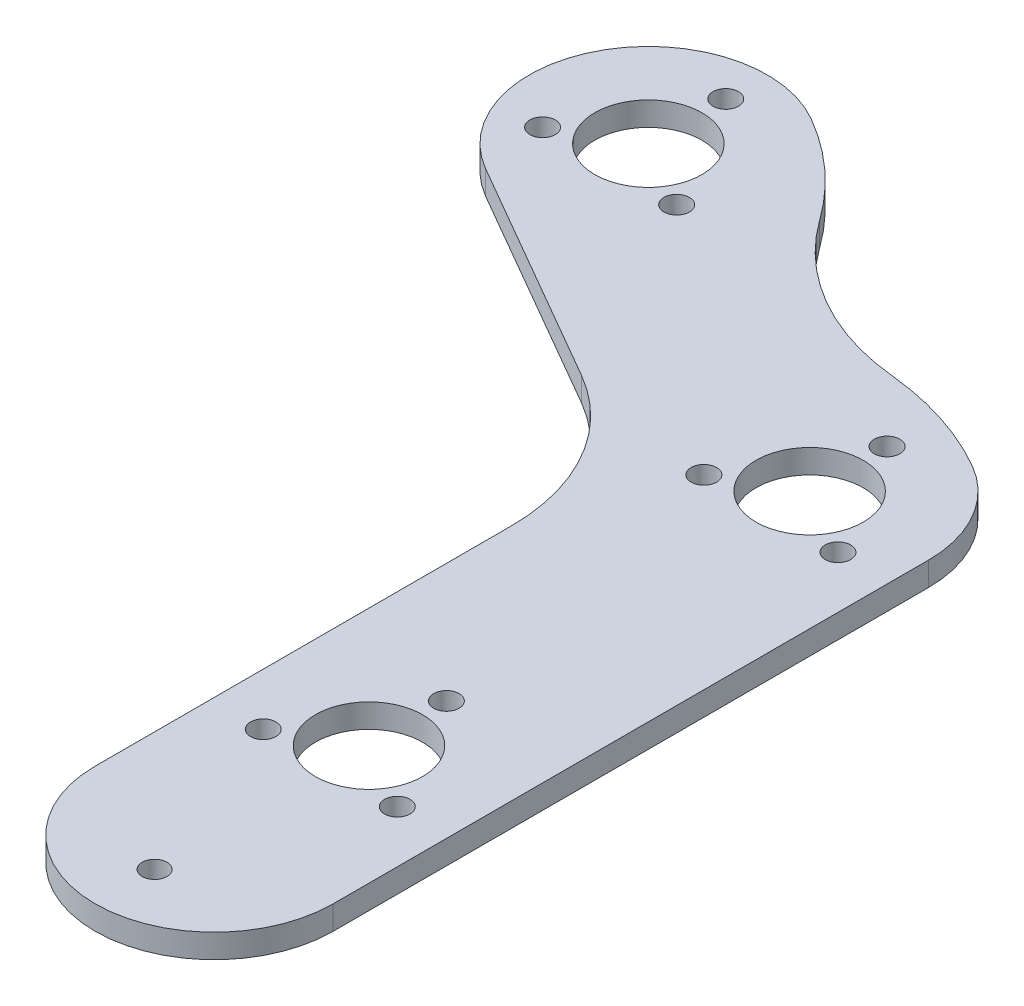
SolidWorks part; units mm, degrees
material "PC High Viscosity"
ref_plane "Front Plane" through (0, 0, 0) normal (0, 0, 1) x (1, 0, 0)
ref_plane "Top Plane" through (0, 0, 0) normal (0, 1, 0) x (1, 0, 0)
ref_plane "Right Plane" through (0, 0, 0) normal (1, 0, 0) x (0, 0, -1)
sketch "Sketch2" plane through (0, 0, 0) normal (0, 1, 0) x (1, 0, 0)
  line L0 (0, 117.475) -> (0, 0) construction
  line L1 (0, 117.475) -> (-101.7363, 176.2125) construction
  line L2 (31.75, 20.032) -> (31.75, 117.475)
  line L4 (-57.15, 113.8088) -> (-117.6113, 148.7162)
  line L5 (-59.8623, 248.7404) -> (-151.9577, 89.2265) construction
  line L6 (-85.8613, 203.7088) -> (15.875, 144.9713) construction
  line L7 (59.941, 221.2959) -> (-45.6102, 38.4758) construction
  line L8 (-50.8682, 146.8437) -> (-34.9932, 174.3401) construction
  line L9 (-34.9932, 174.3401) -> (22.5602, 274.0254) construction
  line L10 (-31.75, -41.275) -> (-31.75, 69.8147)
  line L11 (31.75, 20.032) -> (31.75, -41.275)
  circle A1 centre (0, 0) radius 14.2875
  circle A2 centre (0, 117.475) radius 14.2875
  circle A3 centre (-101.7363, 176.2125) radius 14.2875
  arc A5 (-117.6113, 148.7162) -> (-85.8613, 203.7088) centre (-101.7363, 176.2125) cw
  arc A6 (31.75, 117.475) -> (15.875, 144.9713) centre (0, 117.475) ccw
  arc A7 (-31.75, 69.8147) -> (-57.15, 113.8088) centre (-82.55, 69.8147) ccw
  circle A8 centre (-101.7363, 176.2125) radius 50.8 construction
  circle A9 centre (0, 117.475) radius 50.8 construction
  arc A12 (31.75, -41.275) -> (-31.75, -41.275) centre (0, -41.275) cw
  circle A16 centre (0, -57.15) radius 3.302
  arc A18 (15.875, 144.9713) -> (-15.7886, 155.1371) centre (-23.4652, 76.832) ccw
  arc A19 (-15.7886, 155.1371) -> (-61.2257, 181.3702) centre (-9.5932, 218.3341) cw
  arc A20 (-61.2257, 181.3702) -> (-85.8613, 203.7088) centre (-125.2016, 135.5695) ccw
  circle A21 centre (-17.8726, -10.3187) radius 3.3909
  circle A22 centre (0, 20.6375) radius 3.3909
  circle A23 centre (17.8726, -10.3187) radius 3.3909
  circle A24 centre (-17.8726, 107.1563) radius 3.3909
  circle A25 centre (-119.6089, 165.8938) radius 3.3909
  circle A26 centre (0, 138.1125) radius 3.3909
  circle A27 centre (17.8726, 107.1563) radius 3.3909
  circle A28 centre (-101.7363, 196.85) radius 3.3909
  circle A29 centre (-83.8637, 165.8938) radius 3.3909
  point P43 (0, 0)
  point P51 (0, 117.475)
  point P59 (-101.7363, 176.2125)
  dimension "D2" = 28.575
  dimension "1.125" = 28.575
  dimension "D6" = 31.75
  dimension "D7" = 101.6
  dimension "D8" = 41.275
  dimension "D9" = 50.8
  dimension "D10" = 63.5
  dimension "D11" = 6.7818
  dimension "D12" = 120
  dimension "D3" = 31.75
  dimension "D13" = 117.475
  dimension "1.25" = 6.604
  dimension "D4" = 50.8
  dimension "D17" = 6.7818
  dimension "D18" = 6.7818
  dimension "D20" = 6.35
  dimension "D22" = 6.35
  dimension "D5" = 117.475
  dimension "D14" = 6.35
  dimension "D15" = 57.15
  dimension "D16" = 3
  dimension "D19" = 3
  dimension "D21" = 3
extrude "Boss-Extrude1" add sketch "Sketch2" along normal blind 6.35
